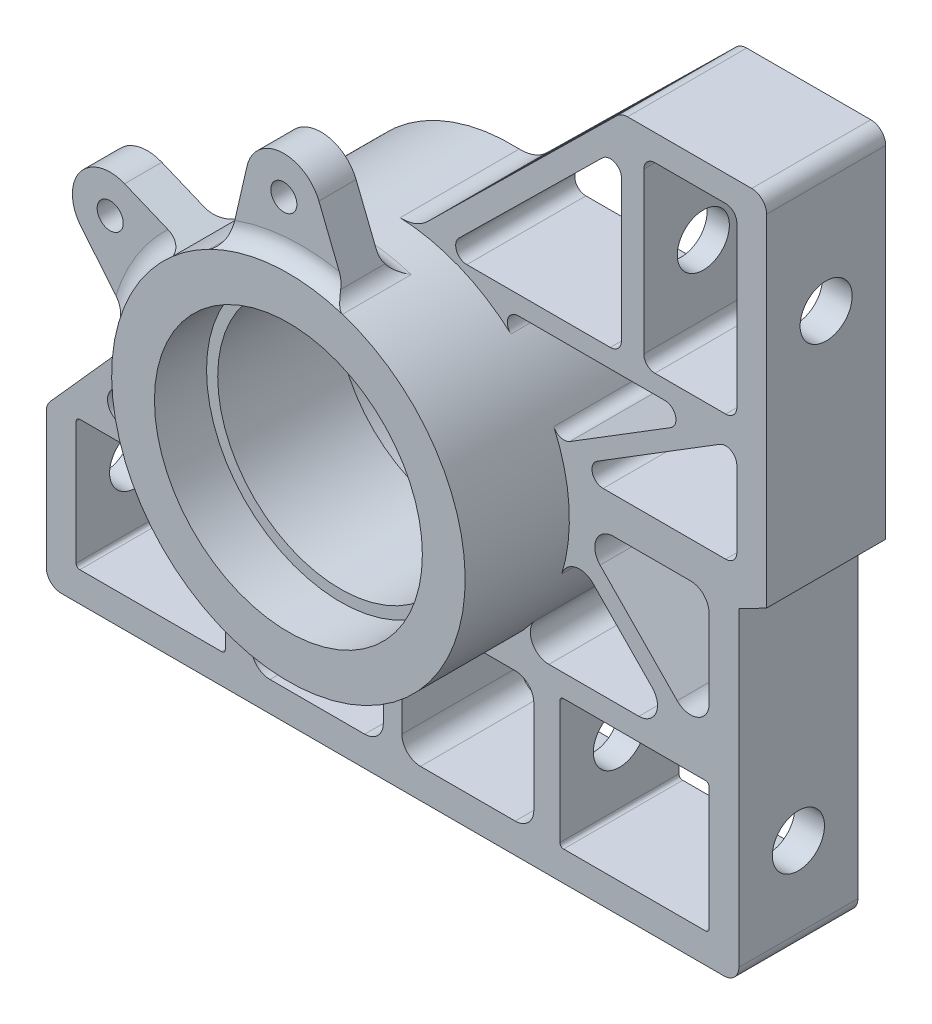
SolidWorks part; units mm, degrees
material "7075-T6 (SN)"
ref_plane "Front Plane" through (0, 0, 0) normal (0, 0, 1) x (1, 0, 0)
ref_plane "Top Plane" through (0, 0, 0) normal (0, 1, 0) x (1, 0, 0)
ref_plane "Right Plane" through (0, 0, 0) normal (1, 0, 0) x (0, 0, -1)
sketch "Sketch1" plane through (0, 0, 0) normal (0, 0, 1) x (1, 0, 0)
  circle A0 centre (0, 0) radius 36
  circle A1 centre (0, 0) radius 47.5
  dimension "D1" = 72
  dimension "D2" = 95
extrude "Boss-Extrude1" add sketch "Sketch1" along normal blind 60
sketch "Sketch2" plane through (0, 0, 0) normal (0, 0, -1) x (-1, 0, 0)
  line L0 (0, 0) -> (0, -85.5) construction
  line L1 (-89.05, -85.5) -> (89.05, -85.5)
  line L2 (93.05, -81.5) -> (93.05, -45.0252)
  line L4 (-63.1377, 101.5) -> (-96.5, 101.5)
  line L6 (-65, -60) -> (65, -60) construction
  line L7 (-65, -60) -> (-65, 70) construction
  line L8 (-65, 70) -> (-80, 70) construction
  line L9 (-84.05, -77.5) -> (-45.95, -77.5)
  line L10 (-85.05, -76.5) -> (-85.05, -43.5)
  line L11 (-84.05, -42.5) -> (-45.95, -42.5)
  line L12 (-44.95, -76.5) -> (-44.95, -43.5)
  line L13 (-85.05, -77.5) -> (-44.95, -42.5) construction
  line L14 (-85.05, -42.5) -> (-44.95, -77.5) construction
  line L15 (45.95, -77.5) -> (84.05, -77.5)
  line L16 (44.95, -76.5) -> (44.95, -43.5)
  line L17 (45.95, -42.5) -> (84.05, -42.5)
  line L18 (85.05, -76.5) -> (85.05, -43.5)
  line L19 (44.95, -77.5) -> (85.05, -42.5) construction
  line L20 (44.95, -42.5) -> (85.05, -77.5) construction
  line L25 (-100.5, 97.5) -> (-100.5, 5.8481)
  line L26 (-89.5, 94.5) -> (-70.5, 94.5)
  line L27 (-92.5, 91.5) -> (-92.5, 48.5)
  line L28 (-89.5, 45.5) -> (-70.5, 45.5)
  line L29 (-67.5, 91.5) -> (-67.5, 48.5)
  line L30 (-92.5, 94.5) -> (-67.5, 45.5) construction
  line L31 (-92.5, 45.5) -> (-67.5, 94.5) construction
  line L32 (-93.05, -81.5) -> (-93.05, 1.9641)
  line L33 (-93.05, 1.9641) -> (-100.5, 5.8481)
  line L34 (92.0346, -42.362) -> (46.7544, 8.3829)
  line L35 (-60.3325, 100.3515) -> (-6.1946, 47.0943)
  line L36 (-61.5, 86.425) -> (-61.5, 48.5)
  line L37 (-58.5, 45.5) -> (-19.9478, 45.5)
  line L38 (-17.844, 50.6386) -> (-56.3961, 88.5636)
  line L39 (-92.5, 35.114) -> (-92.5, 14.7271)
  line L40 (-89.5, 11.7271) -> (-56.5736, 11.7271)
  line L41 (-54.9943, 17.2778) -> (-87.9207, 37.6647)
  line L42 (-74.7284, 34.9493) -> (-47.6317, 18.172)
  line L43 (-73.1491, 40.5) -> (-33.8231, 40.5)
  line L44 (-85.05, -3.0359) -> (-85.05, -24.2301)
  line L45 (-76.4741, -27.7248) -> (-55.7612, -6.5306)
  line L46 (-59.3371, 1.9641) -> (-80.05, 1.9641)
  line L47 (-69.757, -28.0053) -> (-53.8273, -11.7055)
  line L60 (-66.1811, -36.5) -> (-42, -36.5)
  line L68 (53.6007, -6.837) -> (75.599, -31.4902)
  line L69 (72.6144, -38.1534) -> (49.95, -38.1534)
  line L71 (44.95, -33.1534) -> (44.95, -15.3541)
  line L72 (-32.95, -77.5) -> (-7.5, -77.5)
  line L73 (-2.5, -72.5) -> (-2.5, -47.4342)
  line L74 (-37.95, -72.5) -> (-37.95, -47.5)
  line L75 (-32.95, -42.5) -> (-21.2132, -42.5)
  line L76 (2.5, -72.5) -> (2.5, -47.4342)
  line L77 (7.5, -77.5) -> (32.9501, -77.5)
  line L78 (37.95, -72.5331) -> (37.95, -28.5665)
  circle A0 centre (0, 0) radius 47.5 construction
  arc A1 (24.8193, 40.5) -> (-44.6143, 16.3038) centre (0, 0) ccw construction
  arc A2 (-31.8138, 35.2723) -> (-43.3166, 19.4916) centre (0, 0) ccw
  arc A3 (-46.0296, 11.7271) -> (-47.4974, 0.497) centre (0, 0) ccw construction
  arc A4 (-45.4656, -13.7526) -> (-38, -28.5) centre (0, 0) ccw
  arc A5 (-47.2398, -4.965) -> (-30.3974, -36.5) centre (0, 0) ccw construction
  circle A7 centre (0, 0) radius 47.5
  arc A9 (7.4649, -46.9098) -> (37.95, -28.5665) centre (0, 0) ccw construction
  arc A10 (44.3531, -17.0017) -> (46.9996, -6.8768) centre (0, 0) ccw
  arc A11 (43.2647, -19.6065) -> (46.6848, -8.7623) centre (0, 0) ccw construction
  arc A12 (-33.8144, -33.3592) -> (-11.3105, -46.1337) centre (0, 0) ccw
  arc A13 (-37.95, -28.5665) -> (-7.4649, -46.9098) centre (0, 0) ccw construction
  arc A16 (-45.95, -77.5) -> (-44.95, -76.5) centre (-45.95, -76.5) ccw
  arc A17 (-84.05, -77.5) -> (-85.05, -76.5) centre (-84.05, -76.5) cw
  arc A18 (-85.05, -43.5) -> (-84.05, -42.5) centre (-84.05, -43.5) cw
  arc A19 (-45.95, -42.5) -> (-44.95, -43.5) centre (-45.95, -43.5) cw
  arc A20 (45.95, -77.5) -> (44.95, -76.5) centre (45.95, -76.5) cw
  arc A21 (84.05, -77.5) -> (85.05, -76.5) centre (84.05, -76.5) ccw
  arc A22 (84.05, -42.5) -> (85.05, -43.5) centre (84.05, -43.5) cw
  arc A23 (44.95, -43.5) -> (45.95, -42.5) centre (45.95, -43.5) cw
  arc A24 (-70.5, 45.5) -> (-67.5, 48.5) centre (-70.5, 48.5) ccw
  arc A25 (-92.5, 48.5) -> (-89.5, 45.5) centre (-89.5, 48.5) ccw
  arc A26 (-89.5, 94.5) -> (-92.5, 91.5) centre (-89.5, 91.5) ccw
  arc A27 (-70.5, 94.5) -> (-67.5, 91.5) centre (-70.5, 91.5) cw
  arc A28 (-19.9478, 45.5) -> (-17.844, 50.6386) centre (-19.9478, 48.5) ccw
  arc A29 (-61.5, 48.5) -> (-58.5, 45.5) centre (-58.5, 48.5) ccw
  arc A30 (-61.5, 86.425) -> (-56.3961, 88.5636) centre (-58.5, 86.425) cw
  arc A31 (-47.6317, 18.172) -> (-43.3166, 19.4916) centre (-46.0524, 20.7226) ccw
  arc A32 (-74.7284, 34.9493) -> (-73.1491, 40.5) centre (-73.1491, 37.5) cw
  arc A33 (-33.8231, 40.5) -> (-31.8138, 35.2723) centre (-33.8231, 37.5) cw
  arc A34 (-92.5, 14.7271) -> (-89.5, 11.7271) centre (-89.5, 14.7271) ccw
  arc A35 (-56.5736, 11.7271) -> (-54.9943, 17.2778) centre (-56.5736, 14.7271) ccw
  arc A36 (-92.5, 35.114) -> (-87.9207, 37.6647) centre (-89.5, 35.114) cw
  arc A37 (-42, -36.5) -> (-38, -28.5) centre (-42, -31.5) ccw
  arc A38 (-53.8273, -11.7055) -> (-45.4656, -13.7526) centre (-50.2514, -15.2002) cw
  arc A39 (-69.757, -28.0053) -> (-66.1811, -36.5) centre (-66.1811, -31.5) ccw
  arc A40 (-85.05, -24.2301) -> (-76.4741, -27.7248) centre (-80.05, -24.2301) ccw
  arc A41 (-55.7612, -6.5306) -> (-59.3371, 1.9641) centre (-59.3371, -3.0359) ccw
  arc A42 (-85.05, -3.0359) -> (-80.05, 1.9641) centre (-80.05, -3.0359) cw
  arc A61 (89.05, -85.5) -> (93.05, -81.5) centre (89.05, -81.5) ccw
  arc A62 (-89.05, -85.5) -> (-93.05, -81.5) centre (-89.05, -81.5) cw
  arc A64 (93.05, -45.0252) -> (92.0346, -42.362) centre (89.05, -45.0252) ccw
  arc A65 (-60.3325, 100.3515) -> (-63.1377, 101.5) centre (-63.1377, 97.5) ccw
  arc A66 (-96.5, 101.5) -> (-100.5, 97.5) centre (-96.5, 97.5) ccw
  arc A67 (49.95, -38.1534) -> (44.95, -33.1534) centre (49.95, -33.1534) cw
  arc A69 (32.9501, -77.5) -> (37.95, -72.5331) centre (32.9501, -72.5) ccw
  arc A70 (2.5, -72.5) -> (7.5, -77.5) centre (7.5, -72.5) ccw
  arc A71 (-7.5, -77.5) -> (-2.5, -72.5) centre (-7.5, -72.5) ccw
  arc A72 (-32.95, -77.5) -> (-37.95, -72.5) centre (-32.95, -72.5) cw
  arc A73 (-37.95, -47.5) -> (-32.95, -42.5) centre (-32.95, -47.5) cw
  arc A74 (53.6007, -6.837) -> (46.6848, -8.7623) centre (50.6162, -9.5002) ccw
  arc A75 (75.599, -31.4902) -> (72.6144, -38.1534) centre (72.6144, -34.1534) cw
  point P6 (0, -85.5)
  point P125 (-92.5, 40.5)
  point P136 (-85.05, -36.5)
  point P139 (-47.4594, 1.9641)
  point P150 (2.5, -77.5)
  point P154 (-2.5, -77.5)
  point P163 (47.5, 0)
  point P164 (85.05, -44.3653)
  point P165 (33.4574, -33.7173)
  point P197 (93.05, -85.5)
  point P203 (93.05, -43.5)
  point P206 (-61.5, 101.5)
  point P209 (-100.5, 101.5)
  dimension "D16" = 95
  dimension "D18" = 5
  dimension "D25" = 1
  dimension "D26" = 1
  dimension "D27" = 3
  dimension "D28" = 3
  dimension "D29" = 3
  dimension "D30" = 3
  dimension "D31" = 5
  dimension "D35" = 4
  dimension "D36" = 4
  dimension "D7" = 7
  dimension "D5" = 7
  dimension "D20" = 47.5
  dimension "D21" = 5
  dimension "D22" = 4
  dimension "D1" = 130
  dimension "D3" = 130
  dimension "D4" = 33
  dimension "D6" = 40.1
  dimension "D8" = 35
  dimension "D9" = 7
  dimension "D10" = 15
  dimension "D11" = 25
  dimension "D12" = 49
  dimension "D13" = 8
  dimension "8" = 8
  dimension "D14" = 8
  dimension "D15" = 39
  dimension "D17" = 73.5289
  dimension "D19" = 6
  dimension "D23" = 42
  dimension "D24" = 0
  dimension "D37" = 5
  dimension "D38" = 5
extrude "Boss-Extrude2" add sketch "Sketch2" against normal blind 32
sketch3d "3DSketch1" plane through (0, 0, 0) normal (0, 0, 1) x (1, 0, 0)
  dimension "D1" = 10
sketch "Sketch3" plane through (0, 0, 50) normal (0, 0, 1) x (1, 0, 0)
  line L0 (-4.7305, 61.146) -> (-51.4002, 33.455) construction
  line L1 (-28.0653, 47.3005) -> (0, 0) construction
  line L2 (4.6933, 64.9164) -> (12.5436, 45.2952)
  line L3 (-4.7305, 61.146) -> (0, 0) construction
  line L4 (-14.622, 63.4221) -> (-19.361, 42.827)
  line L5 (-28.3103, 37.517) -> (-48.6575, 43.2274)
  line L6 (-51.4002, 33.455) -> (0, 0) construction
  line L7 (-45.7664, 10.6975) -> (-59.2255, 26.9908)
  circle A0 centre (0, 0) radius 61.3287 construction
  circle A1 centre (-4.7305, 61.146) radius 3.5
  circle A2 centre (-51.4002, 33.455) radius 3.5
  circle A3 centre (-4.7305, 61.146) radius 10.15
  circle A4 centre (-51.4002, 33.455) radius 10.15
  circle A5 centre (0, 0) radius 47
  point P7 (-28.0653, 47.3005)
  dimension "D1" = 55
  dimension "D2" = 20.3
  dimension "D3" = 7
  dimension "D6" = 20.3
  dimension "D8" = 16
  dimension "D9" = 94
  dimension "D4" = 54.2665
  dimension "D5" = 54.2665
  dimension "D7" = 16
fillet "Fillet4" radius 10 1 edges at (6.1946, 47.0943, 16)
sketch "Sketch4" plane through (100.5, 0, 0) normal (1, 0, 0) x (0, 0, -1)
  line L0 (-16, 94.5) -> (-16, 45.5) construction
  line L2 (-32, 94.5) -> (0, 94.5) construction
  line L3 (-32, 45.5) -> (0, 45.5) construction
  line L4 (-32, 94.5) -> (0, 94.5)
  line L5 (-32, 45.5) -> (0, 45.5)
  circle A1 centre (-16, 67) radius 7
  point P4 (-16, 70)
  dimension "D1" = 14
  dimension "D2" = 3
extrude "Cut-Extrude1" cut sketch "Sketch4" against normal up to surface (39 mm away) contours L0 A1 | A1 L0 up to face at (61.5, 67.4625, 16)
sketch "Sketch5" plane through (93.05, 0, 0) normal (1, 0, 0) x (0, 0, -1)
  line L0 (-32, -77.5) -> (0, -77.5) construction
  line L1 (-32, -42.5) -> (0, -42.5) construction
  line L2 (-32, -77.5) -> (0, -77.5)
  line L3 (-32, -42.5) -> (0, -42.5)
  line L4 (-16, -42.5) -> (-16, -77.5) construction
  circle A0 centre (-16, -60) radius 7
  dimension "D1" = 14
extrude "Cut-Extrude2" cut sketch "Sketch5" against normal blind 64 contours L4 A0 | A0 L4
mirror "Mirror1" about plane through (0, 0, 0) normal (1, 0, 0) of "Cut-Extrude2"
ref_plane "Plane1" through (0, 0, 30) normal (0, 0, -1) x (-1, 0, 0)
sketch "Sketch6" plane through (0, 0, 30) normal (0, 0, -1) x (-1, 0, 0)
  circle A0 centre (0, 0) radius 36
  circle A1 centre (0, 0) radius 33
  dimension "D1" = 66
extrude "Boss-Extrude4" add sketch "Sketch6" along normal blind 16 and the other way blind 16
fillet "Fillet5" radius 4 3 edges at (2.5, -47.4342, 16) (-2.5, -47.4342, 16) (-37.95, -28.5665, 16)
ref_plane "Plane2" through (0, 0, 56.5) normal (0, 0, 1) x (1, 0, 0)
sketch "Sketch8" plane through (0, 0, 56.5) normal (0, 0, 1) x (1, 0, 0)
  line L0 (-4.7267, 61.1436) -> (-51.3974, 33.4542) construction
  line L1 (-28.0621, 47.2989) -> (0, 0) construction
  line L2 (4.6946, 64.913) -> (12.5436, 45.2952)
  line L3 (-4.7267, 61.1436) -> (0, 0) construction
  line L4 (-14.6154, 63.4202) -> (-19.3561, 42.8292)
  line L6 (-51.3974, 33.4542) -> (0, 0) construction
  line L7 (-45.7661, 10.6988) -> (-59.223, 26.9902)
  line L8 (-30.4779, 35.7784) -> (-48.0729, 43.0634)
  line L9 (-48.0729, 43.0634) -> (-48.6548, 43.2267)
  circle A0 centre (0, 0) radius 61.326 construction
  circle A1 centre (-4.7267, 61.1436) radius 3.5
  circle A2 centre (-51.3974, 33.4542) radius 3.5
  circle A3 centre (-4.7267, 61.1436) radius 10.1474
  circle A4 centre (-51.3974, 33.4542) radius 10.15
  circle A5 centre (0, 0) radius 47
  point P6 (-28.0621, 47.2989)
  dimension "D1" = 54.2665
extrude "Boss-Extrude6" add sketch "Sketch8" against normal blind 10
fillet "Fillet12" radius 5 7 edges at (-3.6611, 47.3587, 46.5) (12.3109, 45.8769, 51.5) (-3.6611, 47.3587, 56.5) (-19.2155, 43.4398, 51.5) (-40.526, 24.7768, 46.5) (-40.526, 24.7768, 56.5) (-46.1651, 11.1819, 51.5)
ref_plane "Plane3" through (0, 0, 86.5) normal (0, 0, 1) x (1, 0, 0)
mirror "Mirror2" about plane through (0, 0, 86.5) normal (0, 0, 1) of bodies 112
delete or keep bodies "Body-Delete/Keep 1" type delete bodies bodies 113
